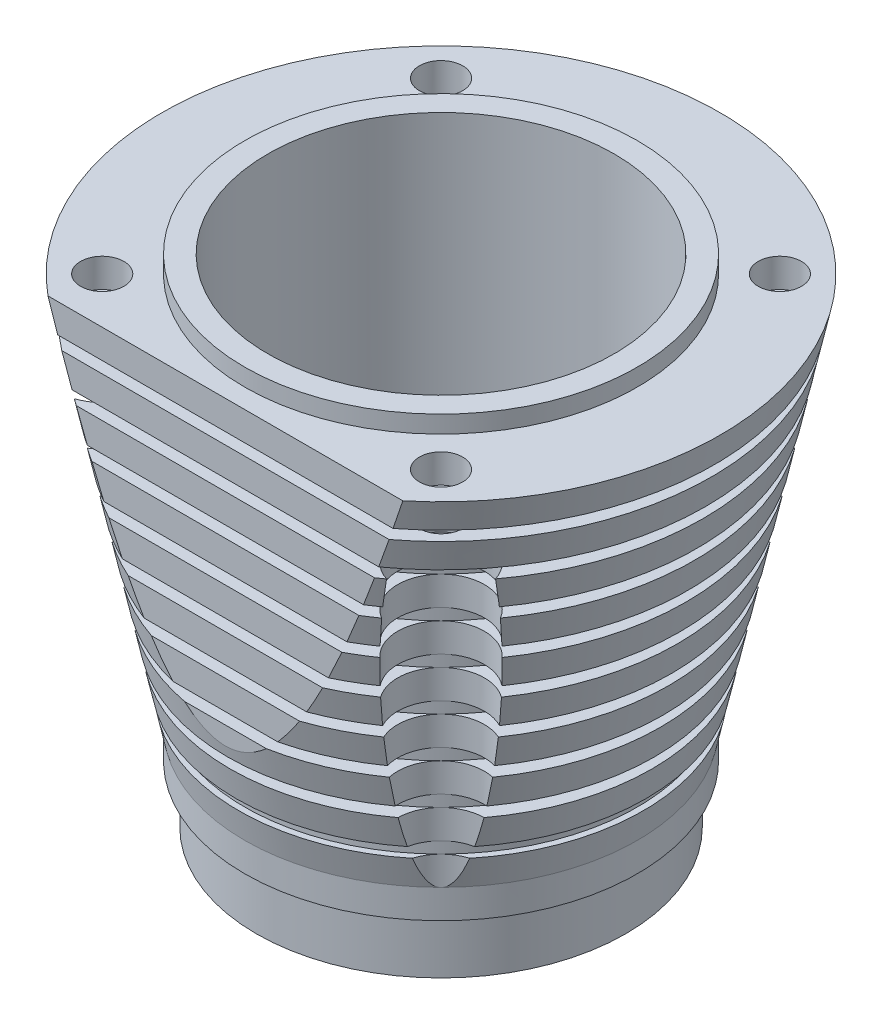
SolidWorks part; units mm, degrees
ref_plane "Front Plane" through (0, 0, 0) normal (0, 0, 1) x (1, 0, 0)
ref_plane "Top Plane" through (0, 0, 0) normal (0, 1, 0) x (1, 0, 0)
ref_plane "Right Plane" through (0, 0, 0) normal (1, 0, 0) x (0, 0, -1)
sketch "Sketch3" plane through (0, 0, 0) normal (0, 0, 1) x (1, 0, 0)
  line L0 (30, 0) -> (30, -8)
  line L1 (30, -8) -> (49, -8)
  line L2 (49, -8) -> (49, -3)
  line L3 (49, -3) -> (34, -3)
  line L4 (34, -3) -> (34, 0)
  line L5 (34, 0) -> (30, 0)
  line L6 (0, 0) -> (0, 13.9872) construction
  dimension "InternalRadius" = 30
  dimension "WallThickness" = 4
  dimension "FinHeight" = 15
  dimension "GrooveWidth" = 3
  dimension "FinWidth" = 5
  dimension "TotalWidth" = 8
revolve "Revolve1" add sketch "Sketch3" angle 360 about L6
pattern_linear "LPattern1" count 10 spacing 7 along (0, -1, 0) of "Revolve1"
sketch "Sketch4" plane through (0, 0, 0) normal (0, 0, 1) x (1, 0, 0)
  line L1 (49, 0) -> (34, -71)
  line L8 (49, 0) -> (49, -71)
  line L9 (34, -71) -> (49, -71)
  dimension "Offset1" = 15
  dimension "TaperHeight" = 71
  dimension "Offset2" = 15
revolve "Cut-Revolve1" cut sketch "Sketch4" angle 360 about L0
sketch "Sketch5" plane through (0, 0, 0) normal (0, 1, 0) x (1, 0, 0)
  circle A41 centre (29.3449, -29.3449) radius 3.75
  circle A48 centre (-29.3449, -29.3449) radius 3.75
  circle A49 centre (-29.3449, 29.3449) radius 3.75
  circle A50 centre (29.3449, 29.3449) radius 3.75
  dimension "HoleDiameter" = 7.5
  dimension "PitchDiameter" = 41.5
  dimension "D1" = 4
extrude "Cut-Extrude5" cut sketch "Sketch5" against normal through all
sketch "Sketch19" plane through (0, -15, 0) normal (0, -1, 0) x (1, 0, 0)
  circle A0 centre (-29.3449, 29.3449) radius 7.5
  circle A1 centre (29.3449, 29.3449) radius 7.5
  circle A2 centre (29.3449, -29.3449) radius 7.5
  circle A3 centre (-29.3449, -29.3449) radius 7.5
  dimension "PitchDiameter" = 41.5
  dimension "BoreDiameter" = 15
  dimension "D2" = 4
extrude "Cut-Extrude13" cut sketch "Sketch19" along normal through all
sketch "Sketch14" plane through (0, -3, 0) normal (0, 1, 0) x (1, 0, 0)
  line L0 (-100, -37.35) -> (100, -37.35)
  line L1 (-100, -37.35) -> (-100, -67.35)
  line L2 (100, -37.35) -> (100, -67.35)
  line L3 (-100, -67.35) -> (100, -67.35)
  point P0 (0, -67.35)
  dimension "CuttingLength" = 200
  dimension "CuttingWidth" = 30
  dimension "OffsetLength" = 37.35
extrude "Cut-Extrude12" cut sketch "Sketch14" against normal through all
sketch "Sketch18" plane through (0, 0, 0) normal (0, 0, 1) x (1, 0, 0)
  line L0 (34, -71) -> (34, -76)
  line L1 (30, -71) -> (34, -71)
  line L5 (34, -76) -> (32, -76)
  line L6 (32, -76) -> (32, -86)
  line L7 (32, -86) -> (30, -86)
  line L8 (30, -86) -> (30, -71)
  dimension "HorizontalOffset" = 30
  dimension "InnerThickness" = 2
  dimension "OuterThickness" = 4
  dimension "CylinderHeight" = 76
  dimension "VerticalOffset" = 71
  dimension "CaseHeight" = 15
revolve "Revolve2" add sketch "Sketch18" angle 360 about L0
sketch "Centreline" plane through (0, 0, 0) normal (0, 0, 1) x (1, 0, 0)
  line L0 (0, 0) -> (0, -109.9456) construction
equation "\"Offset1@Sketch4\" = \"FinHeight@Sketch3\""
equation "\"OffsetLength@Sketch14\" = \"PitchDiameter@Sketch5\" * 0.9"
equation "\"PitchDiameter@Sketch5\" = \"InternalRadius@Sketch3\" + \"WallThickness@Sketch3\" +  ( \"FinHeight@Sketch3\" / 2 ) "
equation "\"Offset2@Sketch4\" = \"Offset1@Sketch4\""
equation "\"HorizontalOffset@Sketch18\" = \"InternalRadius@Sketch3\""
equation "\"OuterThickness@Sketch18\" = \"WallThickness@Sketch3\""
equation "\"InnerThickness@Sketch18\" = \"OuterThickness@Sketch18\" / 2"
equation "\"PatternCount@LPattern1\" =  ( \"CylinderHeight@Sketch18\" - 5 )  / \"PatternSpacing@LPattern1\""
equation "\"VerticalOffset@Sketch18\" =  ( \"GrooveWidth@Sketch3\" + \"FinWidth@Sketch3\" )  +  ( \"PatternCount@LPattern1\" - 1 )  * \"PatternSpacing@LPattern1\""
equation "\"TaperHeight@Sketch4\" = \"VerticalOffset@Sketch18\""
equation "\"PitchDiameter@Sketch19\" = \"PitchDiameter@Sketch5\""
equation "\"PatternSpacing@LPattern1\" = \"GrooveWidth@Sketch3\" + \"FinWidth@Sketch3\" - 1"
